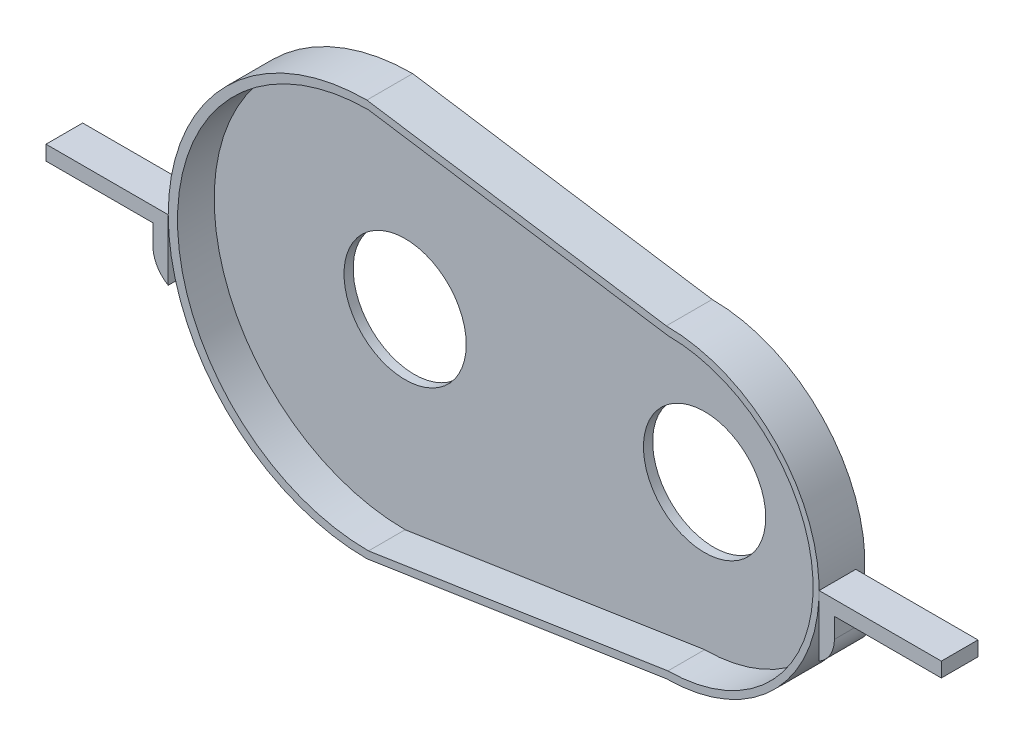
SolidWorks part; units mm, degrees
ref_plane "Front Plane" through (0, 0, 0) normal (0, 0, 1) x (1, 0, 0)
ref_plane "Top Plane" through (0, 0, 0) normal (0, 1, 0) x (1, 0, 0)
ref_plane "Right Plane" through (0, 0, 0) normal (1, 0, 0) x (0, 0, -1)
sketch "Sketch1" plane through (0, 0, 0) normal (0, 0, 1) x (1, 0, 0)
  line L0 (-56.3934, 65) -> (41.6066, 50)
  line L1 (-56.3934, -65) -> (41.6066, -50)
  line L2 (-56.3934, -62.5) -> (41.6066, -47.5)
  line L3 (-56.3934, 62.5) -> (41.6066, 47.5)
  arc A0 (-56.3934, 65) -> (-56.3934, -65) centre (-56.3934, 0) ccw
  arc A1 (41.6066, -50) -> (41.6066, 50) centre (41.6066, 0) ccw
  arc A2 (-56.3934, 62.5) -> (-56.3934, -62.5) centre (-56.3934, 0) ccw
  arc A3 (41.6066, -47.5) -> (41.6066, 47.5) centre (41.6066, 0) ccw
  circle A4 centre (-56.3934, 0) radius 20
  circle A5 centre (41.6066, 0) radius 20
  dimension "D2" = 130
  dimension "D3" = 100
  dimension "D4" = 125
  dimension "D5" = 95
  dimension "D6" = 40
  dimension "D7" = 40
  dimension "D1" = 98
extrude "Boss-Extrude1" add sketch "Sketch1" against normal blind 15 contours L1 A1 L0 A0
sketch "Sketch2" plane through (0, 0, 0) normal (0, 0, 1) x (1, 0, 0)
  line L0 (-55.8513, 62.5) -> (42.1487, 47.5)
  line L1 (-55.8513, -62.5) -> (42.1487, -47.5)
  arc A0 (-55.8513, 62.5) -> (-55.8513, -62.5) centre (-55.8513, 0) ccw
  arc A1 (42.1487, -47.5) -> (42.1487, 47.5) centre (42.1487, 0) ccw
  dimension "D2" = 95
  dimension "D3" = 125
  dimension "D1" = 98
extrude "Cut-Extrude1" cut sketch "Sketch2" against normal blind 12
sketch "Sketch3" plane through (0, 0, -12) normal (0, 0, 1) x (1, 0, 0)
  circle A0 centre (-55.8702, 0) radius 20
  circle A1 centre (42.1298, 0) radius 20
  dimension "D2" = 40
  dimension "D3" = 40
  dimension "D1" = 98
extrude "Cut-Extrude2" cut sketch "Sketch3" against normal blind 12
sketch "Sketch4" plane through (0, 0, -12) normal (0, 0, 1) x (1, 0, 0)
  line L0 (-161.3934, 0) -> (-121.3934, 0)
  line L1 (-121.3934, 0) -> (-121.3934, -20)
  line L2 (-121.3934, -20) -> (-126.3934, -20)
  line L3 (-126.3934, -20) -> (-126.3934, -4.8015)
  line L4 (-126.3934, -4.8015) -> (-161.3934, -4.8015)
  line L5 (-161.3934, -4.8015) -> (-161.3934, 0)
  line L6 (-161.3934, 0) -> (-161.7999, -1.1425)
  line L7 (91.6066, 0) -> (131.6066, 0)
  line L8 (131.6066, 0) -> (131.6066, -4.8015)
  line L9 (131.6066, -4.8015) -> (96.6066, -4.8015)
  line L10 (96.6066, -4.8015) -> (96.6066, -20)
  line L11 (96.6066, -20) -> (91.6066, -20)
  line L12 (91.6066, -20) -> (91.6066, 0)
  arc A0 (-56.3934, 65) -> (-56.3934, -65) centre (-56.3934, 0) ccw construction
  arc A1 (41.6066, -50) -> (41.6066, 50) centre (41.6066, 0) ccw construction
  dimension "D1" = 40
  dimension "D2" = 5
  dimension "D3" = 20
  dimension "D4" = 40
  dimension "D5" = 20
  dimension "D6" = 5
extrude "Boss-Extrude2" add sketch "Sketch4" along normal blind 12 separate body contours L9 L10 L11 L12 L7 L8 | L0 L1 L2 L3 L4 L5
fillet "Fillet1" radius 10 1 edges at (-126.3934, -20, -6)
fillet "Fillet2" radius 10 1 edges at (96.6066, -20, -6)
